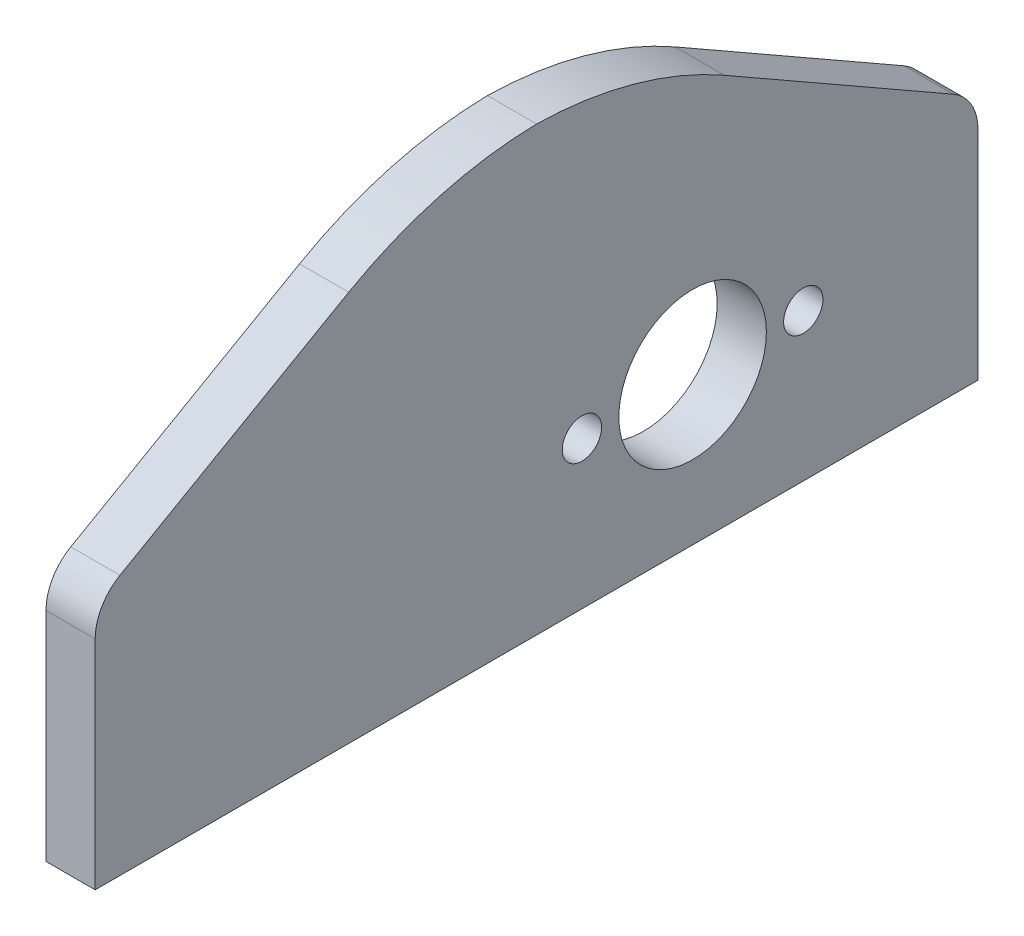
SolidWorks part; units mm, degrees
ref_plane "Спереди" through (0, 0, 0) normal (0, 0, 1) x (1, 0, 0)
ref_plane "Сверху" through (0, 0, 0) normal (0, 1, 0) x (1, 0, 0)
ref_plane "Справа" through (0, 0, 0) normal (1, 0, 0) x (0, 0, -1)
sketch "Эскиз1" plane through (0, 0, 0) normal (1, 0, 0) x (0, 0, -1)
  line L0 (-17.95, 0) -> (-3.95, 8)
  line L1 (-3.95, 8) -> (3.95, 8)
  line L2 (-17.95, 0) -> (-17.95, -10)
  line L3 (-17.95, -10) -> (17.95, -10)
  line L4 (17.95, 0) -> (17.95, -10)
  line L5 (-12.0509, 3.3709) -> (17.95, -10) construction
  line L6 (-17.95, -10) -> (12.0509, 3.3709) construction
  line L7 (3.95, 8) -> (17.95, 0)
  circle A0 centre (0, 0) radius 3.5 construction
  point P0 (0, -2)
  point P11 (17.1016, 12.7266)
  point P12 (0, 0)
  point P14 (0, -2)
  dimension "D2" = 7
  dimension "D1" = 35.9
  dimension "D3" = 10
  dimension "D4" = 18
  dimension "D5" = 10
  dimension "D6" = 10
  dimension "D7" = 14
  dimension "D8" = 8
  dimension "D9" = 17.95
  dimension "D10" = 14
  dimension "D11" = 17.95
extrude "Бобышка-Вытянуть1" add sketch "Эскиз1" along normal blind 2
sketch "Эскиз2" plane through (2, 0, 0) normal (1, 0, 0) x (0, 0, -1)
  line L0 (-17.95, -10) -> (17.95, -10) construction
  line L1 (0, -4) -> (15.7252, -4) construction
  line L2 (0, 8) -> (0, -10) construction
  line L3 (3.95, 8) -> (-3.95, 8) construction
  circle A0 centre (0, 0) radius 1 construction
  circle A1 centre (0, 0) radius 7.5 construction
  circle A2 centre (6.3443, -4) radius 3
  circle A3 centre (1.8443, -4) radius 0.8
  circle A4 centre (10.8443, -4) radius 0.8
  dimension "D1" = 2
  dimension "D2" = 15
  dimension "D3" = 6
  dimension "D4" = 6
  dimension "D5" = 1.6
  dimension "D7" = 4.5
  dimension "D8" = 1.6
  dimension "D6" = 4.5
extrude "Вырез-Вытянуть1" cut sketch "Эскиз2" against normal blind 2
fillet "Скругление1" radius 2 2 edges at (1, 0, -17.95) (1, 0, 17.95)
fillet "Скругление3" radius 16 2 edges at (1, 8, -3.95) (1, 8, 3.95)
